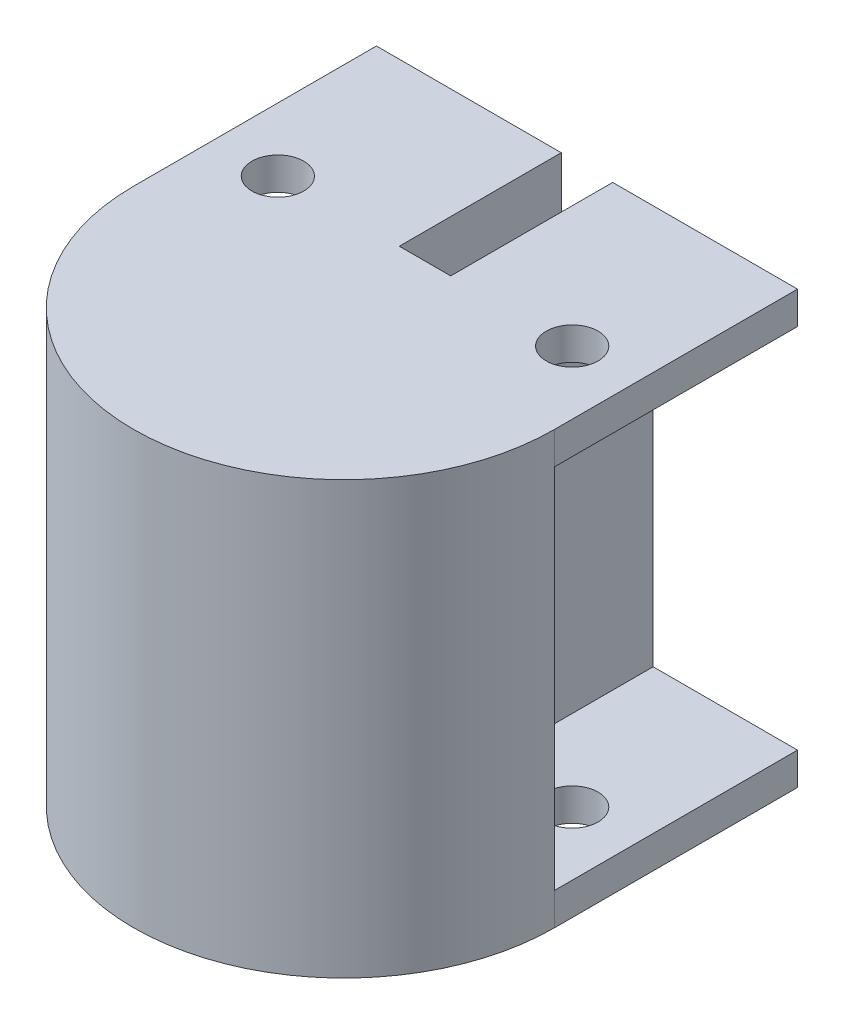
SolidWorks part; units mm, degrees
ref_plane "Front Plane" through (0, 0, 0) normal (0, 0, 1) x (1, 0, 0)
ref_plane "Top Plane" through (0, 0, 0) normal (0, 1, 0) x (1, 0, 0)
ref_plane "Right Plane" through (0, 0, 0) normal (1, 0, 0) x (0, 0, -1)
sketch "Sketch1" plane through (0, 0, 0) normal (0, 1, 0) x (1, 0, 0)
  line L0 (-1.5875, 0) -> (1.5875, 0)
  line L1 (1.5875, 0) -> (1.5875, 10)
  line L2 (1.5875, 10) -> (13, 10)
  line L3 (13, 10) -> (13, -5)
  line L4 (0, 0) -> (0, -18) construction
  line L5 (-13, 10) -> (-13, -5)
  line L6 (-1.5875, 10) -> (-13, 10)
  line L7 (-1.5875, 0) -> (-1.5875, 10)
  arc A0 (-13, -5) -> (13, -5) centre (0, -5) ccw
  circle A1 centre (9.0875, 0) radius 1.6
  circle A2 centre (-9.0875, 0) radius 1.6
  dimension "D5" = 3.2
  dimension "D1" = 1.5875
  dimension "D2" = 11.4125
  dimension "D3" = 15
  dimension "D4" = 10
  dimension "D6" = 7.5
extrude "Boss-Extrude1" add sketch "Sketch1" along normal blind 2
sketch "Sketch3" plane through (0, 0, 0) normal (0, -1, 0) x (1, 0, 0)
  line L0 (4.0875, -10) -> (1.5875, -10)
  line L1 (13, -10) -> (1.5875, -10) construction
  line L2 (1.5875, -10) -> (1.5875, 0)
  line L3 (1.5875, 0) -> (-1.5875, 0)
  line L4 (-1.5875, 0) -> (-1.5875, -10)
  line L5 (-1.5875, -10) -> (-4.0875, -10)
  line L6 (-1.5875, -10) -> (-13, -10) construction
  line L7 (-4.0875, -10) -> (-4.0875, 5)
  line L8 (-4.0875, 5) -> (-13, 5)
  line L9 (4.0875, -10) -> (4.0875, 5)
  line L10 (4.0875, 5) -> (13, 5)
  arc A0 (13, 5) -> (-13, 5) centre (0, 5) ccw
  dimension "D1" = 2.5
extrude "Boss-Extrude3" add sketch "Sketch3" along normal blind 11.325
ref_plane "Plane2" through (0, -11.325, 0) normal (0, -1, 0) x (-1, 0, 0)
mirror "Mirror11" about plane through (0, -11.325, 0) normal (0, -1, 0) of "Boss-Extrude3"
mirror "Mirror12" about plane through (0, -11.325, 0) normal (0, -1, 0) of "Boss-Extrude1"
